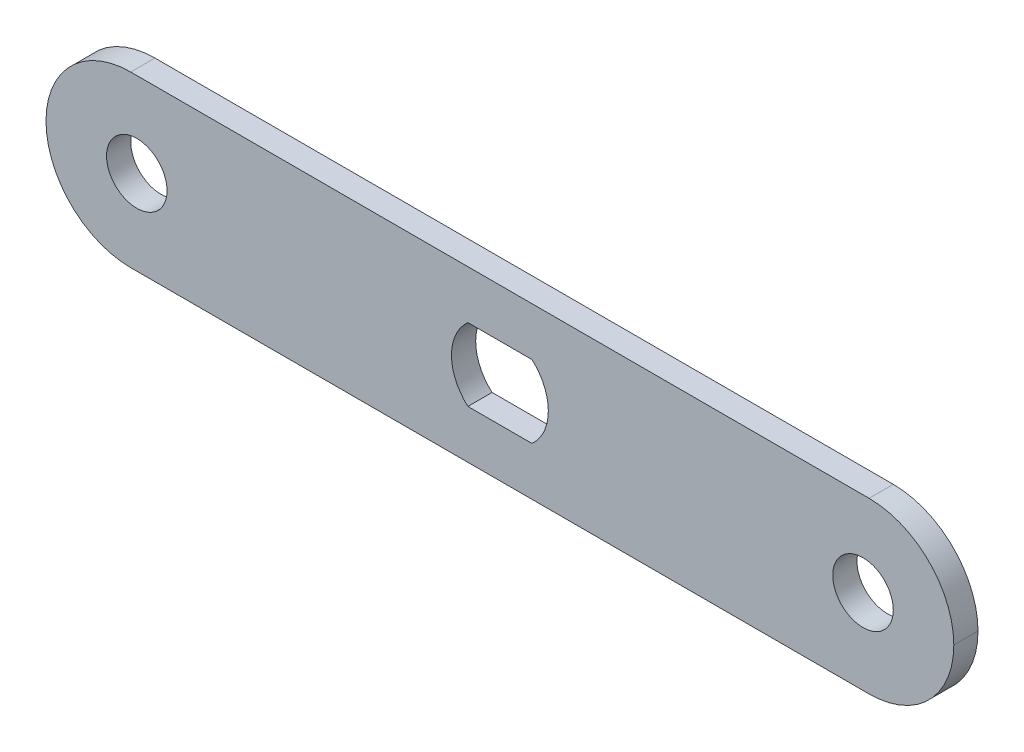
SolidWorks part; units mm, degrees
ref_plane "前视基准面" through (0, 0, 0) normal (0, 0, 1) x (1, 0, 0)
ref_plane "上视基准面" through (0, 0, 0) normal (0, 1, 0) x (1, 0, 0)
ref_plane "右视基准面" through (0, 0, 0) normal (1, 0, 0) x (0, 0, -1)
sketch "草图1" plane through (0, 0, 0) normal (0, 0, 1) x (1, 0, 0)
  line L1 (-2.6458, 3) -> (2.6458, 3)
  line L2 (-2.6458, -3) -> (2.6458, -3)
  arc A2 (2.6458, 3) -> (2.6458, -3) centre (0, 0) cw
  arc A3 (-2.6458, 3) -> (-2.6458, -3) centre (0, 0) ccw
  point P7 (0, 0)
  point P10 (0, 3)
  point P13 (0, -3)
extrude "凸台-拉伸1" add sketch "草图1" along normal blind 2
sketch "草图2" plane through (0, 0, 2) normal (0, 0, 1) x (1, 0, 0)
  line L2 (-37.5, 7) -> (-37.5, -7)
  line L4 (37.5, 7) -> (37.5, -7)
  line L5 (-37.5, 7) -> (37.5, -7) construction
  line L6 (-37.5, -7) -> (37.5, 7) construction
  line L12 (-37.5, 7) -> (37.5, 7)
  line L13 (-37.5, -7) -> (37.5, -7)
  circle A0 centre (-30, 0) radius 2.5
  circle A1 centre (30, 0) radius 2.5
  point P0 (0, 0)
  point P10 (0, 0)
extrude "凸台-拉伸2" add sketch "草图2" against normal blind 2
sketch "草图3" plane through (0, 0, 0) normal (0, 0, 1) x (1, 0, 0)
  line L1 (-2.6458, 3) -> (2.6458, 3)
  line L2 (-2.6458, -3) -> (2.6458, -3)
  arc A2 (2.6458, 3) -> (2.6458, -3) centre (0, 0) cw
  arc A3 (-2.6458, 3) -> (-2.6458, -3) centre (0, 0) ccw
  point P7 (0, 0)
  point P10 (0, 3)
  point P13 (0, -3)
extrude "切除-拉伸2" cut sketch "草图3" along normal through all
fillet "圆角1" radius 7 4 edges at (37.5, -7, 1) (37.5, 7, 1) (-37.5, -7, 1) (-37.5, 7, 1)
